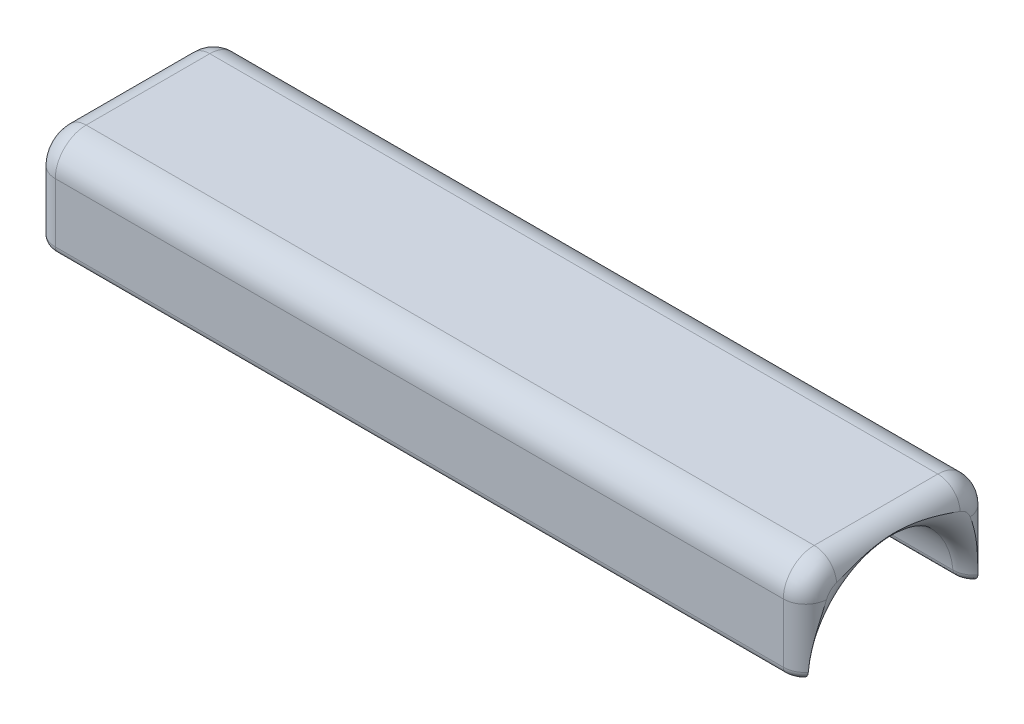
SolidWorks part; units mm, degrees
ref_plane "Front Plane" through (0, 0, 0) normal (0, 0, 1) x (1, 0, 0)
ref_plane "Top Plane" through (0, 0, 0) normal (0, 1, 0) x (1, 0, 0)
ref_plane "Right Plane" through (0, 0, 0) normal (1, 0, 0) x (0, 0, -1)
sketch "Sketch1" plane through (0, 0, 0) normal (0, 1, 0) x (1, 0, 0)
  line L1 (-95.25, 22.86) -> (95.25, 22.86)
  line L2 (-95.25, 22.86) -> (-95.25, -22.86)
  line L3 (-95.25, -22.86) -> (95.25, -22.86)
  line L4 (95.25, 22.86) -> (95.25, -22.86)
  line L5 (-95.25, 22.86) -> (95.25, -22.86) construction
  line L6 (-95.25, -22.86) -> (95.25, 22.86) construction
  point P0 (0, 0)
  dimension "D1" = 45.72
  dimension "D2" = 190.5
extrude "Boss-Extrude1" add sketch "Sketch1" along normal blind 24.13
sketch "Sketch2" plane through (-95.25, 0, 0) normal (-1, 0, 0) x (0, 0, 1)
  line L0 (-22.86, 0) -> (22.86, 0) construction
  circle A0 centre (0, 0) radius 19.05
  dimension "D1" = 38.1
extrude "Cut-Extrude1" cut sketch "Sketch2" against normal up to next contours A0
fillet "Fillet2" radius 7.62 2 edges at (0, 24.13, 22.86) (0, 24.13, -22.86)
fillet "Fillet4" radius 5.5118 8 edges at (-95.25, 19.05, 0) (-95.25, 21.8982, -20.6282) (-95.25, 24.13, 0) (-95.25, 21.8982, 20.6282) (95.25, 21.8982, -20.6282) (95.25, 19.05, 0) (95.25, 21.8982, 20.6282) (95.25, 24.13, 0)
fillet "Fillet5" radius 1.9431 12 edges at (92.0295, 0, 19.5488) (-92.0295, 0, 19.5488) (-92.0295, 0, 22.3612) (92.0295, 0, 22.3612) (92.0295, 0, -19.5488) (92.0295, 0, -22.3612) (0, 0, -22.86) (-92.0295, 0, -22.3612) (-92.0295, 0, -19.5488) (0, 0, -19.05) (0, 0, 19.05) (0, 0, 22.86)
